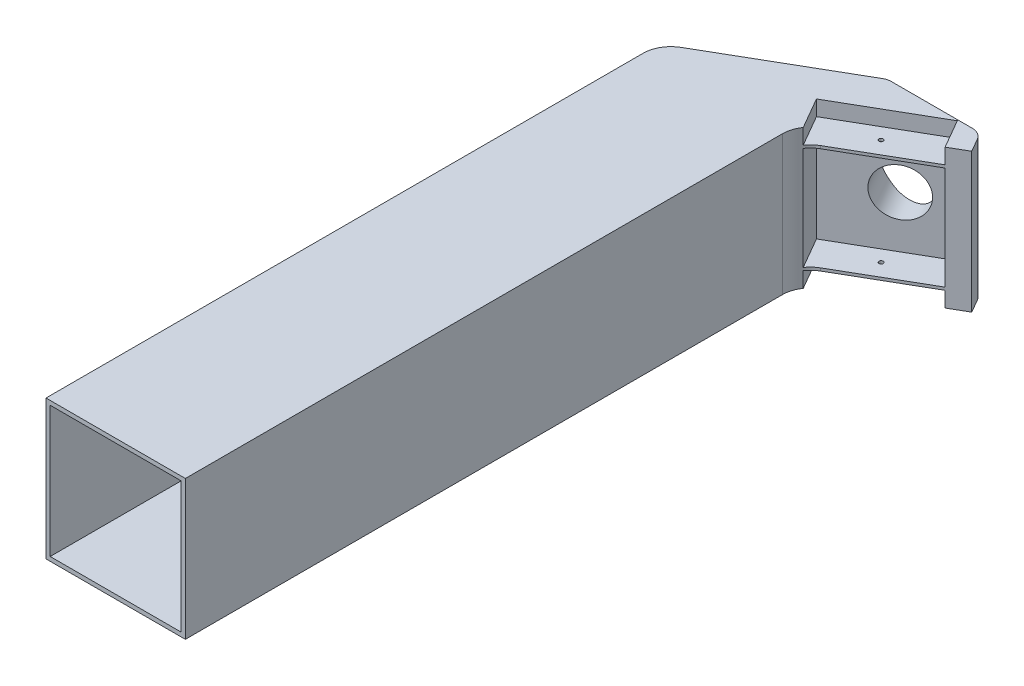
SolidWorks part; units mm, degrees
ref_plane "前视基准面" through (0, 0, 0) normal (0, 0, 1) x (1, 0, 0)
ref_plane "上视基准面" through (0, 0, 0) normal (0, 1, 0) x (1, 0, 0)
ref_plane "右视基准面" through (0, 0, 0) normal (1, 0, 0) x (0, 0, -1)
sketch "草图1" plane through (0, 0, 0) normal (0, 0, 1) x (1, 0, 0)
  line L1 (25, -25) -> (-25, -25)
  line L2 (25, -25) -> (25, 25)
  line L3 (25, 25) -> (-25, 25)
  line L4 (-25, -25) -> (-25, 25)
  line L5 (25, -25) -> (-25, 25) construction
  line L6 (25, 25) -> (-25, -25) construction
  point P0 (0, 0)
  dimension "D1" = 50
  dimension "D2" = 50
extrude "凸台-拉伸1" add sketch "草图1" along normal blind 220 contours L2 L1 L4 L3
sketch "草图3" plane through (0, 25, 0) normal (0, 1, 0) x (1, 0, 0)
  line L0 (25, 0) -> (-25, 0) construction
  line L1 (25, 0) -> (-25, 0)
  line L2 (-25, -220) -> (-25, 0) construction
  line L3 (-25, -220) -> (-25, 0)
  line L4 (-25, 0) -> (26.9615, 30)
  line L5 (26.9615, 30) -> (76.9615, 30)
  line L6 (76.9615, 30) -> (25, 0)
  dimension "D1" = 30
  dimension "D2" = 250
  dimension "D3" = 50
extrude "凸台-拉伸2" add sketch "草图3" against normal up to surface (50 mm away) contours L4 L5 L6 L1 up to face at (0, -25, 110)
sketch "草图4" plane through (6.25, 0, 10.8253) normal (0.5, 0, 0.866) x (0.866, 0, -0.5)
  line L0 (81.6506, 25) -> (21.6506, 25) construction
  line L1 (60.1506, -18.5) -> (23.1506, -18.5)
  line L2 (60.1506, -18.5) -> (60.1506, 18.5)
  line L3 (60.1506, 18.5) -> (23.1506, 18.5)
  line L4 (23.1506, -18.5) -> (23.1506, 18.5)
  line L5 (60.1506, -18.5) -> (23.1506, 18.5) construction
  line L6 (60.1506, 18.5) -> (23.1506, -18.5) construction
  line L7 (81.6506, -25) -> (21.6506, -25) construction
  line L8 (81.6506, -25) -> (81.6506, 25) construction
  point P0 (41.6506, 0)
  dimension "D1" = 6.5
  dimension "D2" = 6.5
  dimension "D3" = 37
  dimension "D4" = 40
extrude "切除-拉伸2" cut sketch "草图4" against normal blind 12 contours L2 L1 L4 L3
sketch "草图5" plane through (0.25, 0, 0.433) normal (0.5, 0, 0.866) x (0.866, 0, -0.5)
  line L0 (60.1506, -18.5) -> (60.1506, 18.5) construction
  line L2 (60.1506, -18.5) -> (23.1506, -18.5) construction
  circle A0 centre (45.1506, 0) radius 8.5
  dimension "D2" = 17
  dimension "D1" = 15
  dimension "D3" = 18.5
extrude "切除-拉伸3" cut sketch "草图5" against normal up to surface (13 mm away) up to face at (0.9808, 0, -15)
sketch "草图7" plane through (0, -18.5, 0) normal (0, 1, 0) x (1, 0, 0)
  line L0 (52.342, 29.6423) -> (20.299, 11.1423) construction
  line L1 (20.299, 11.1423) -> (26.299, 0.75) construction
  circle A0 centre (39.1705, 15.456) radius 0.75
  dimension "D1" = 1.5
  dimension "D2" = 18.5
  dimension "D3" = 5.7
sketch "草图8" plane through (0, 18.5, 0) normal (0, -1, 0) x (1, 0, 0)
  line L0 (52.342, -29.6423) -> (20.299, -11.1423) construction
  line L1 (52.342, -29.6423) -> (58.342, -19.25) construction
  circle A0 centre (39.1705, -15.456) radius 0.75
  dimension "D1" = 1.5
  dimension "D2" = 5.7
  dimension "D3" = 18.5
extrude "切除-拉伸4" cut sketch "草图8" against normal up to surface (6.5 mm away) contours A0 up to face at (17.3205, 25, 63.3333)
extrude "切除-拉伸5" cut sketch "草图7" against normal up to surface (6.5 mm away) up to face at (17.3205, -25, 63.3333)
sketch "草图10" plane through (0, -25, 0) normal (0, -1, 0) x (1, 0, 0)
  line L4 (58.342, -19.25) -> (26.299, -0.75)
  line L5 (52.342, -29.6423) -> (58.342, -19.25)
  line L6 (-25, 220) -> (-25, 0)
  line L7 (-25, 0) -> (26.9615, -30)
  line L8 (26.9615, -30) -> (76.9615, -30)
  line L9 (76.9615, -30) -> (25, 0)
  line L10 (25, 0) -> (25, 220)
  line L11 (25, 220) -> (-25, 220)
  line L12 (-25, 220) -> (-25, 0)
  line L13 (-25, 0) -> (26.9615, -30)
  line L14 (26.9615, -30) -> (76.9615, -30)
  line L15 (76.9615, -30) -> (25, 0)
  line L16 (25, 0) -> (25, 220)
  line L17 (25, 220) -> (-25, 220)
  line L18 (20.299, -11.1423) -> (52.342, -29.6423)
  line L19 (26.299, -0.75) -> (20.299, -11.1423)
  line L20 (58.342, -19.25) -> (26.299, -0.75)
  line L21 (52.342, -29.6423) -> (58.342, -19.25)
  line L22 (20.299, -11.1423) -> (52.342, -29.6423)
  line L23 (26.299, -0.75) -> (20.299, -11.1423)
  circle A0 centre (39.1705, -15.456) radius 0.75 construction
  circle A1 centre (39.1705, -15.456) radius 0.75
  dimension "D1" = 0
  dimension "D2" = 0
extrude "切除-拉伸6" cut sketch "草图10" against normal blind 5.5 contours L20 L23 L22 L21
sketch "草图11" plane through (0, 25, 0) normal (0, 1, 0) x (1, 0, 0)
  line L4 (26.299, 0.75) -> (58.342, 19.25)
  line L5 (20.299, 11.1423) -> (26.299, 0.75)
  line L6 (52.342, 29.6423) -> (20.299, 11.1423)
  line L7 (58.342, 19.25) -> (52.342, 29.6423)
  line L8 (26.299, 0.75) -> (58.342, 19.25)
  line L9 (20.299, 11.1423) -> (26.299, 0.75)
  line L10 (52.342, 29.6423) -> (20.299, 11.1423)
  line L11 (58.342, 19.25) -> (52.342, 29.6423)
  dimension "D1" = 0
extrude "切除-拉伸7" cut sketch "草图11" against normal blind 5.5 contours L8 L11 L10 L9
sketch "草图12" plane through (0, -25, 0) normal (0, -1, 0) x (1, 0, 0)
  line L0 (64.4042, -22.75) -> (60.2184, -30)
  line L1 (76.9615, -30) -> (58.342, -19.25) construction
  line L2 (26.9615, -30) -> (76.9615, -30) construction
  line L3 (26.9615, -30) -> (76.9615, -30)
  line L4 (76.9615, -30) -> (58.342, -19.25)
  line L5 (64.4042, -22.75) -> (76.9615, -30)
  line L6 (76.9615, -30) -> (60.2184, -30)
  dimension "D1" = 7
extrude "切除-拉伸8" cut sketch "草图12" against normal up to surface (50 mm away) contours L6 L0 L5 up to face at (26.1205, 25, 31.9215)
fillet "圆角1" radius 5 1 edges at (60.2184, 0, -30)
fillet "圆角2" radius 5 1 edges at (26.9615, -15.0492, -30)
fillet "圆角3" radius 10 1 edges at (-25, 0, 0)
fillet "圆角4" radius 10 1 edges at (25, 0, 0)
sketch "草图13" plane through (0, 0, 220) normal (0, 0, 1) x (1, 0, 0)
  line L0 (25, 25) -> (-25, 25) construction
  line L1 (23.5, -23.5) -> (-23.5, -23.5)
  line L2 (23.5, -23.5) -> (23.5, 23.5)
  line L3 (23.5, 23.5) -> (-23.5, 23.5)
  line L4 (-23.5, -23.5) -> (-23.5, 23.5)
  line L5 (23.5, -23.5) -> (-23.5, 23.5) construction
  line L6 (23.5, 23.5) -> (-23.5, -23.5) construction
  line L7 (-25, -25) -> (-25, 25) construction
  line L12 (25, 25) -> (-25, 25)
  line L13 (-25, 25) -> (-25, -25)
  line L14 (-25, -25) -> (25, -25)
  line L15 (25, -25) -> (25, 25)
  line L16 (25, 25) -> (-25, 25)
  line L17 (-25, 25) -> (-25, -25)
  line L18 (-25, -25) -> (25, -25)
  line L19 (25, -25) -> (25, 25)
  point P0 (0, 0)
  dimension "D1" = 1.5
  dimension "D2" = 1.5
  dimension "D3" = 0
extrude "切除-拉伸9" cut sketch "草图13" against normal blind 50 contours L4 L1 L2 L3
sketch "草图2" plane through (0, 0, 220) normal (0, 0, 1) x (1, 0, 0)
  line L0 (25, 25) -> (-25, 25) construction
  line L1 (21.5, -21.5) -> (-21.5, -21.5)
  line L2 (21.5, -21.5) -> (21.5, 21.5)
  line L3 (21.5, 21.5) -> (-21.5, 21.5)
  line L4 (-21.5, -21.5) -> (-21.5, 21.5)
  line L5 (21.5, -21.5) -> (-21.5, 21.5) construction
  line L6 (21.5, 21.5) -> (-21.5, -21.5) construction
  line L7 (25, -25) -> (25, 25) construction
  point P0 (0, 0)
  dimension "D1" = 3.5
  dimension "D2" = 3.5
extrude "切除-拉伸10" cut sketch "草图2" against normal blind 150
fillet "圆角5" radius 5 1 edges at (26.9615, 15.0492, -30)
